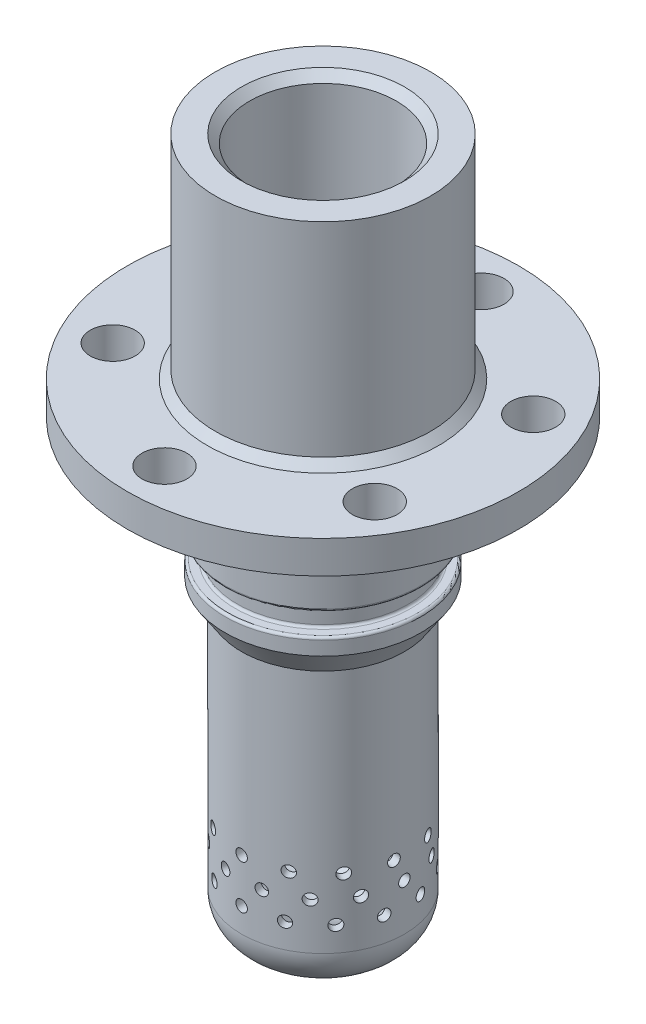
SolidWorks part; units mm, degrees
note: The reader was unsure of these and kept them because the rebuilt part matched: shared geometry of "Szkic3<3>".
ref_plane "Front Plane" through (0, 0, 0) normal (0, 0, 1) x (1, 0, 0)
ref_plane "Top Plane" through (0, 0, 0) normal (0, 1, 0) x (1, 0, 0)
ref_plane "Right Plane" through (0, 0, 0) normal (1, 0, 0) x (0, 0, -1)
sketch "Szkic1" plane through (0, 0, 0) normal (0, 0, 1) x (1, 0, 0)
  line L0 (0, 0) -> (-13.2055, 0)
  line L1 (-24, -30) -> (-12, -30)
  line L2 (-13.2055, 0) -> (-13.2055, -26)
  line L3 (-13.2055, -26) -> (-24, -26)
  line L4 (-24, -26) -> (-24, -30)
  line L5 (-12, -30) -> (-12, -42.3)
  line L6 (-12, -42.3) -> (-10.5, -42.3)
  line L7 (-10.5, -42.3) -> (-10.5, -45)
  line L8 (-10.5, -45) -> (-12, -45)
  line L9 (-12, -45) -> (-12, -47)
  line L10 (-12, -47) -> (-10, -50)
  line L11 (-10, -50) -> (-10, -85)
  line L12 (-10, -85) -> (0, -85)
  line L13 (0, -85) -> (0, 0)
  line L14 (0, -85) -> (-9, -85)
  line L15 (-9, -85) -> (-9, 0)
  line L16 (0, -85) -> (0, -83.5)
  line L17 (0, -83.5) -> (-10, -83.5)
  line L19 (-10, -83.5) -> (-9, -83.5)
  line L20 (0, -83.5) -> (-9, -78.0923)
  line L21 (0, -85) -> (-0.7, -85)
  line L22 (-0.7, -85) -> (-0.7, -80.4628)
  line L23 (-0.7, -80.4628) -> (0, -80.4628)
  dimension "D15" = 59
  dimension "D1" = 13.2055
  dimension "D2" = 12
  dimension "D3" = 26
  dimension "D4" = 24
  dimension "D5" = 4
  dimension "D6" = 12.3
  dimension "D7" = 2.7
  dimension "D8" = 10.5
  dimension "D9" = 2
  dimension "D10" = 10
  dimension "D11" = 3
  dimension "D12" = 35
  dimension "D13" = 9
  dimension "D14" = 1.5
  dimension "D16" = 0.7
revolve "Obrót1" add sketch "Szkic1" angle 360 about L13
fillet "Zaokrąglenie1" radius 5 1 edges at (0, -85, -10)
sketch "Szkic3" plane through (0, 0, 0) normal (0, 0, 1) x (1, 0, 0)
  line L0 (0, 0) -> (0, -85)
  line L1 (9, 0) -> (-9, 0) construction
  line L2 (0, -85) -> (0, -77)
  line L3 (0, -77) -> (0, -74.3)
  line L4 (0, -74.3) -> (0, -71.6)
  circle A0 centre (0, -77) radius 0.7
  circle A1 centre (0, -71.6) radius 0.7
  dimension "D3" = 1.4
  dimension "D6" = 1.4
  dimension "D1" = 85
  dimension "D2" = 8
  dimension "D4" = 10.7
  dimension "D5" = 13.4
extrude "Wytnij-wyciągnięcie1" cut sketch "Szkic3" along normal blind 13 contours A0
pattern_circular "Szyk kołowy1" count 14 over 360 about axis through (0, -85, 0) along (0, -1, 0) of "Wytnij-wyciągnięcie1"
ref_plane "Płaszczyzna1" through (0, 0, 0) normal (0.2225, 0, 0.9749) x (0, 1, 0)
sketch "Szkic4" plane through (0, 0, 0) normal (0.2225, 0, 0.9749) x (0, 1, 0)
  line L0 (-85, 0) -> (-74.3, 0)
  line L1 (-85, 0) -> (0, 0) construction
  circle A0 centre (-74.3, 0) radius 0.7
  dimension "D1" = 1.4
  dimension "D2" = 10.7
extrude "Wytnij-wyciągnięcie2" cut sketch "Szkic4" along normal blind 13 contours A0
pattern_circular "Szyk kołowy2" count 14 over 360 about axis through (0, -85, 0) along (0, -1, 0) of "Wytnij-wyciągnięcie2"
extrude "Wytnij-wyciągnięcie3" cut sketch "Szkic3<3>" along normal blind 13 contours A1
sketch "Szkic3<3>" plane through (0, 0, 0) normal (0, 0, 1) x (1, 0, 0) same geometry as "Szkic3"
pattern_circular "Szyk kołowy3" count 13 over 360 about axis through (0, -85, 0) along (0, -1, 0) of "Wytnij-wyciągnięcie3"
fillet "Zaokrąglenie2" radius 0.3 4 edges at (0, -45, -12) (0, -45, -10.5) (0, -42.3, -12) (0, -42.3, -10.5)
chamfer "Sfazowanie1" distance 1 angle 45 1 edges at (0, -26, -13.2055)
sketch "Szkic5" plane through (0, -26, 0) normal (0, 1, 0) x (1, 0, 0)
  line L0 (0, 0) -> (0.5612, 23.9934)
  line L1 (0, 0) -> (0.4444, 19)
  circle A0 centre (0, 0) radius 24 construction
  circle A1 centre (0.4444, 19) radius 2.75
  dimension "D2" = 5.5
  dimension "D1" = 19
extrude "Wytnij-wyciągnięcie4" cut sketch "Szkic5" against normal blind 13 contours A1
pattern_circular "Szyk kołowy4" count 6 over 360 about axis through (0, 0, 0) along (0, 1, 0) of "Wytnij-wyciągnięcie4"
chamfer "Sfazowanie2" distance 0.4 angle 45 1 edges at (0, -85, -0.7)
chamfer "Sfazowanie3" distance 1 angle 45 1 edges at (0, 0, -9)
